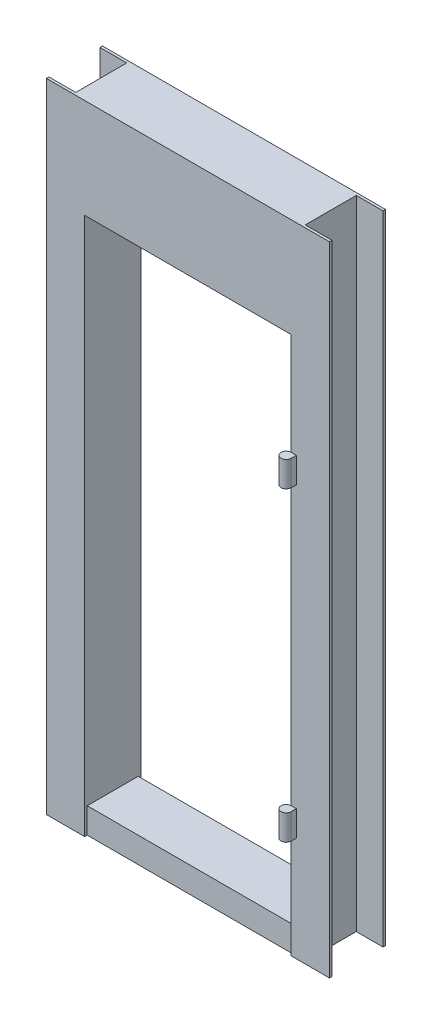
SolidWorks part; units mm, degrees
ref_plane "Спереди" through (0, 0, 0) normal (0, 0, 1) x (1, 0, 0)
ref_plane "Сверху" through (0, 0, 0) normal (0, 1, 0) x (1, 0, 0)
ref_plane "Справа" through (0, 0, 0) normal (1, 0, 0) x (0, 0, -1)
sketch "Эскиз1" plane through (0, 0, 0) normal (0, 0, 1) x (1, 0, 0)
  line L0 (4450, 105) -> (4450, 100) construction
  line L9 (5250, 2105) -> (4450, 2105) construction
  line L10 (5250, 2105) -> (5250, 105) construction
  line L11 (5250, 105) -> (4450, 105) construction
  line L12 (4400, 2500) -> (5300, 2500)
  line L13 (4400, 2500) -> (4400, 0)
  line L14 (4400, 0) -> (5300, 0)
  line L15 (5300, 2500) -> (5300, 0)
  line L17 (4450, 2105) -> (4450, 105) construction
  line L18 (5255, 2110) -> (4445, 2110)
  line L19 (5255, 2110) -> (5255, 100)
  line L20 (5255, 100) -> (4445, 100)
  line L21 (4445, 2110) -> (4445, 100)
  line L22 (4450, 100) -> (4450, 105) construction
  line L23 (4450, 105) -> (4445, 105) construction
  line L24 (5250, 2105) -> (5255, 2105) construction
  line L25 (5250, 2105) -> (5250, 2110) construction
  line L26 (5255, 2110) -> (5300, 2110) construction
  line L27 (4445, 2110) -> (4400, 2110) construction
  dimension "D1" = 800
  dimension "D2" = 2000
  dimension "D3" = 5
  dimension "D4" = 100
extrude "Бобышка-Вытянуть1" add sketch "Эскиз1" against normal blind 200
sketch "Эскиз2" plane through (0, 0, 0) normal (0, 0, 1) x (1, 0, 0)
  line L0 (5255, 2110) -> (5255, 100) construction
  line L1 (5255, 1710) -> (5275, 1710)
  line L2 (5255, 1710) -> (5255, 1610)
  line L3 (5255, 1610) -> (5275, 1610)
  line L4 (5275, 1710) -> (5275, 1610)
  line L5 (5255, 2110) -> (4445, 2110) construction
  dimension "D1" = 400
  dimension "D2" = 100
  dimension "D4" = 20
extrude "Бобышка-Вытянуть2" add sketch "Эскиз2" along normal blind 30
sketch "Эскиз3" plane through (0, 1710, 0) normal (0, 1, 0) x (1, 0, 0)
  circle A0 centre (5255, -30) radius 20
extrude "Бобышка-Вытянуть3" add sketch "Эскиз3" against normal up to surface (100 mm away) up to face at (5265, 1610, 15)
pattern_linear "Линейный массив1" count 2 spacing 1200 along (0, -1, 0) of "Бобышка-Вытянуть2", "Бобышка-Вытянуть3"
ref_plane "Плоскость5" through (0, 0, -100) normal (0, 0, 1) x (1, 0, 0)
sketch "Эскиз4" plane through (0, 0, 0) normal (0, 0, 1) x (1, 0, 0)
  line L0 (4445, 0) -> (4295, 0)
  line L1 (4295, 0) -> (4295, 2500)
  line L2 (4295, 2500) -> (5405, 2500)
  line L3 (4400, 2500) -> (5300, 2500) construction
  line L4 (5405, 2500) -> (5405, 0)
  line L5 (5405, 0) -> (5255, 0)
  line L6 (4400, 0) -> (5300, 0) construction
  line L7 (4445, 0) -> (4445, 2110)
  line L8 (4445, 2110) -> (4445, 100) construction
  line L9 (4445, 2110) -> (5255, 2110)
  line L10 (5255, 2110) -> (5255, 0)
  dimension "D1" = 150
extrude "Бобышка-Вытянуть4" add sketch "Эскиз4" along normal blind 10
mirror "Зеркальное отражение1" about plane through (0, 0, -100) normal (0, 0, 1) of "Бобышка-Вытянуть4"
